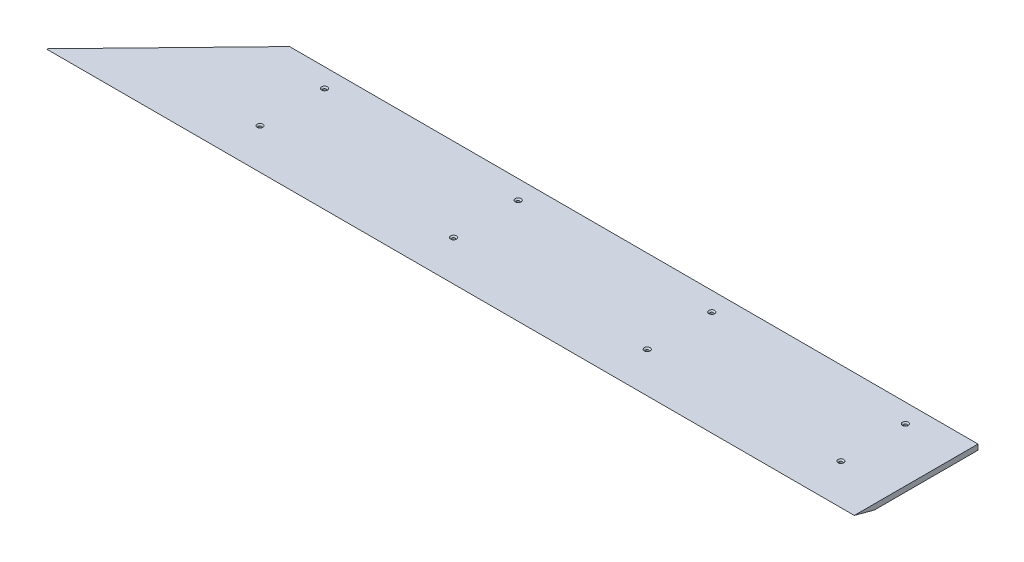
SolidWorks part; units mm, degrees
material "PE High Density"
ref_plane "Front Plane" through (0, 0, 0) normal (0, 0, 1) x (1, 0, 0)
ref_plane "Top Plane" through (0, 0, 0) normal (0, 1, 0) x (1, 0, 0)
ref_plane "Right Plane" through (0, 0, 0) normal (1, 0, 0) x (0, 0, -1)
sketch "Sketch1" plane through (0, 0, 0) normal (0, 1, 0) x (1, 0, 0)
  line L0 (-812.8, 0) -> (812.8, 0)
  line L1 (812.8, 0) -> (812.8, -292.1)
  line L2 (812.8, -292.1) -> (-1095.8646, -292.1)
  line L3 (-1095.8646, -292.1) -> (-812.8, 0)
  point P3 (0, 0)
  dimension "D1" = 1625.6
  dimension "D2" = 292.1
  dimension "D3" = 90
  dimension "D4" = 45.9
extrude "Boss-Extrude1" add sketch "Sketch1" along normal blind 12.7
chamfer "Chamfer1" distance 12.7 angle 75 1 edges at (-141.5323, 0, 292.1) first distance on face at (-141.5323, 6.35, 292.1)
hole_wizard "CSK for 1/4 Flat Head Machine Screw (100)1" positions "Sketch2" profile "Sketch3" countersink size "1/4" standard "ANSI Inch" end condition through all
sketch "Sketch2" plane through (0, 12.7, 0) normal (0, 1, 0) x (1, 0, 0)
  line L0 (812.8, 0) -> (-812.8, 0) construction
  point P0 (-685.8, -44.45)
  point P2 (-685.8, -196.85)
  dimension "D1" = 685.8
  dimension "D2" = 152.4
  dimension "D3" = 44.45
sketch "Sketch3" plane through (-685.8, 12.7, 44.45) normal (1, 0, 0) x (0, 0, 1)
  line L0 (0, 0) -> (0, 12.7)
  line L1 (0, 12.7) -> (3.5712, 12.7)
  line L2 (3.5712, 12.7) -> (3.5712, 2.7579)
  line L3 (3.5712, 2.7579) -> (6.858, 0)
  line L5 (6.858, 0) -> (0, 0)
  line L6 (-3.5712, 2.7579) -> (-6.858, 0) construction
  line L11 (0, -6.35) -> (0, 107.95) construction
  dimension "Thru Hole Dia." = 7.1425
  dimension "Thru Hole Depth" = 12.7
  dimension "Near C'Sink Dia." = 13.716
  dimension "Near C'Sink Angle" = 100
pattern_linear "LPattern1" count 4 spacing 457.2 along (1, 0, 0) of "CSK for 1/4 Flat Head Machine Screw (100)1"
